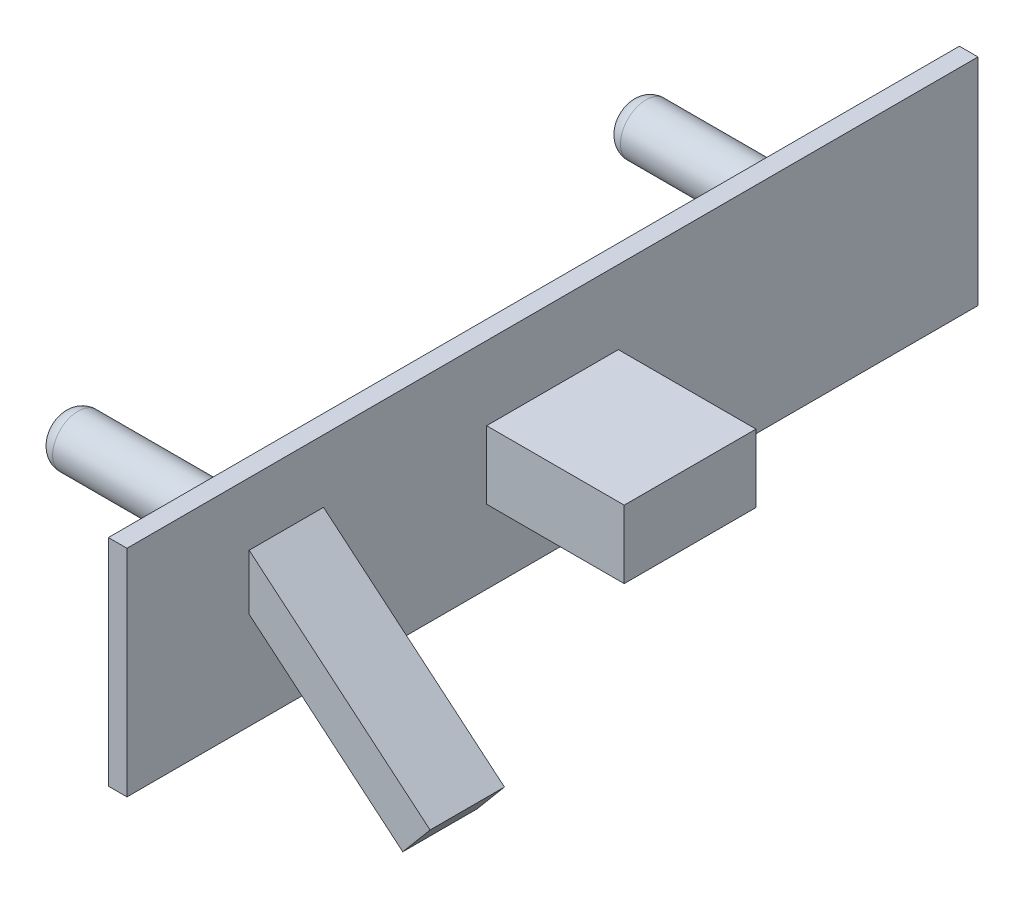
SolidWorks part; units mm, degrees
ref_plane "Front Plane" through (0, 0, 0) normal (0, 0, 1) x (1, 0, 0)
ref_plane "Top Plane" through (0, 0, 0) normal (0, 1, 0) x (1, 0, 0)
ref_plane "Right Plane" through (0, 0, 0) normal (1, 0, 0) x (0, 0, -1)
sketch "Sketch1" plane through (0, 0, 0) normal (1, 0, 0) x (0, 0, -1)
  line L0 (0, 0) -> (80.1, 0)
  line L1 (80.1, 0) -> (80.1, 20.27)
  line L2 (80.1, 20.27) -> (0, 20.27)
  line L3 (0, 20.27) -> (0, 0)
  line L4 (40.05, 20.27) -> (40.05, 0) construction
  line L6 (33.85, 6.935) -> (46.25, 6.935)
  line L7 (33.85, 6.935) -> (33.85, 13.335)
  line L8 (33.85, 13.335) -> (46.25, 13.335)
  line L9 (46.25, 6.935) -> (46.25, 13.335)
  line L10 (40.05, 13.335) -> (40.05, 6.935) construction
  line L11 (33.85, 10.135) -> (46.25, 10.135) construction
  point P7 (40.05, 10.135)
  dimension "D1" = 80.1
  dimension "D2" = 20.27
  dimension "D3" = 6.4
  dimension "D4" = 12.4
extrude "Boss-Extrude1" add sketch "Sketch1" along normal blind 1.75
extrude "Boss-Extrude2" add sketch "Sketch1<2>" along normal blind 14.7 contours L6 L9 L8 L7 region at (0, 10.135, -40.05)
sketch "Sketch1<2>" plane through (0, 0, 0) normal (1, 0, 0) x (0, 0, -1) same geometry as "Sketch1"
ref_plane "Plane1" through (1.0269, -0.8617, 0) normal (0.766, -0.6428, 0) x (0, 0, -1)
sketch "Sketch2" plane through (1.0269, -0.8617, 0) normal (0.766, -0.6428, 0) x (0, 0, -1)
  line L0 (0, 1.1249) -> (14.033, 1.1249) construction
  line L1 (0, 1.1249) -> (80.1, 1.1249) construction
  line L2 (15, 1.1249) -> (15, 8.1249) construction
  line L4 (11.5, 12.1249) -> (18.5, 12.1249)
  line L5 (11.5, 12.1249) -> (11.5, 8.1249)
  line L6 (11.5, 8.1249) -> (18.5, 8.1249)
  line L7 (18.5, 12.1249) -> (18.5, 8.1249)
  point P11 (15, 8.1249)
  dimension "D1" = 7
  dimension "D2" = 15
  dimension "D3" = 7
  dimension "D4" = 4
extrude "Boss-Extrude3" add sketch "Sketch2" against normal up to next and the other way blind 13
sketch "Sketch3" plane through (0, 0, 0) normal (-1, 0, 0) x (0, 0, 1)
  line L0 (-80.1, 10.15) -> (0, 10.15) construction
  line L1 (-80.1, 0) -> (-80.1, 20.27) construction
  line L2 (0, 20.27) -> (0, 0) construction
  line L3 (0, 0) -> (-80.1, 0) construction
  line L4 (-11.8, 10.15) -> (-11.8, 15.0522) construction
  line L5 (-68.7, 10.15) -> (-68.7, 16.3269) construction
  line L6 (-11.8, 12.55) -> (-11.8, 16.9374) construction
  line L7 (-14.2, 10.15) -> (-20.7383, 10.15) construction
  line L8 (-68.7, 12.55) -> (-68.7, 15.4132) construction
  line L9 (-66.3, 10.15) -> (-59.1759, 10.15) construction
  circle A0 centre (-14.2, 12.55) radius 2.4
  circle A1 centre (-66.3, 12.55) radius 2.4
  dimension "D4" = 4.8
  dimension "D1" = 10.15
  dimension "D2" = 11.8
  dimension "D3" = 11.4
extrude "Boss-Extrude4" add sketch "Sketch3" along normal blind 18.55 contours A0 region at (0, 12.55, -14.2)
extrude "Boss-Extrude5" add sketch "Sketch3<3>" along normal blind 17.2 contours A1 region at (0, 12.55, -66.3)
sketch "Sketch3<3>" plane through (0, 0, 0) normal (-1, 0, 0) x (0, 0, 1) same geometry as "Sketch3"
fillet "Fillet1" radius 1.5 2 edges at (-17.2, 12.55, -63.9) (-18.55, 12.55, -11.8)
